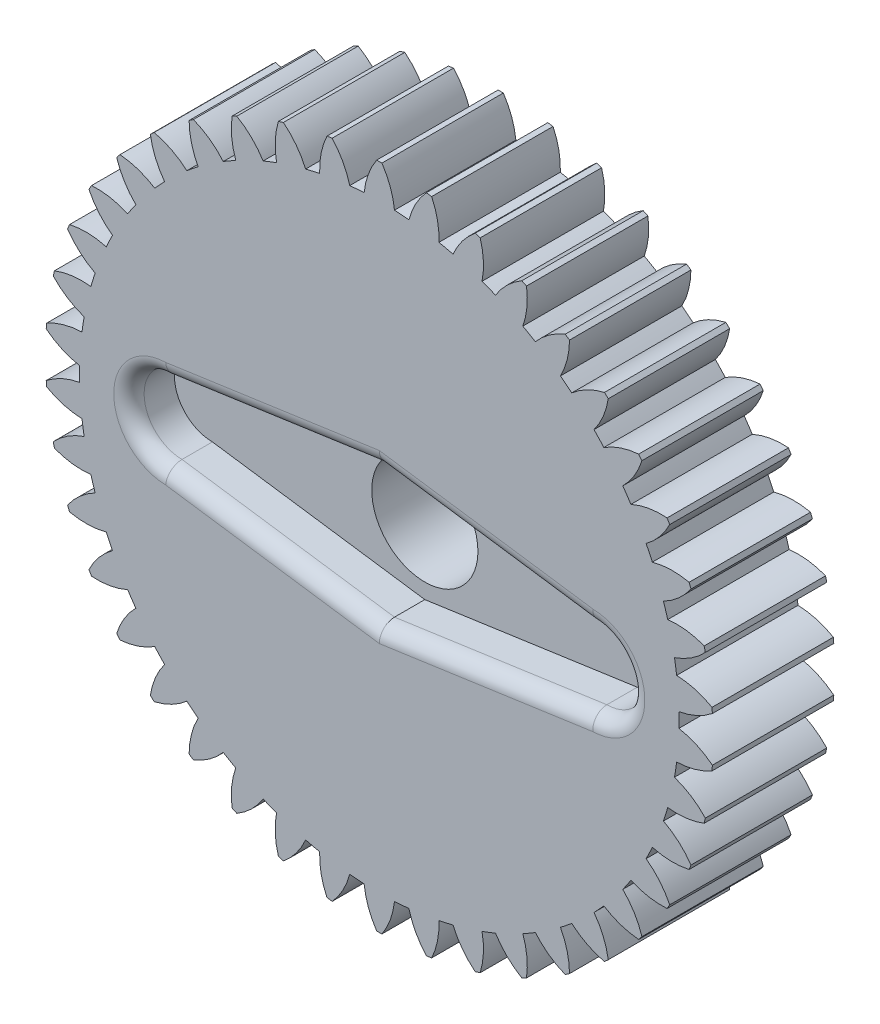
SolidWorks part; units mm, degrees
ref_plane "Front Plane" through (0, 0, 0) normal (0, 0, 1) x (1, 0, 0)
ref_plane "Top Plane" through (0, 0, 0) normal (0, 1, 0) x (1, 0, 0)
ref_plane "Right Plane" through (0, 0, 0) normal (1, 0, 0) x (0, 0, -1)
sketch "Sketch1" plane through (0, 0, 0) normal (0, 0, 1) x (1, 0, 0)
  line L0 (0, 0) -> (0, 23.4828) construction
  line L1 (0.1718, 22) -> (-0.1718, 22)
  line L2 (-1, 19.7247) -> (-0.1718, 22) construction
  line L3 (0.1718, 22) -> (1, 19.7247) construction
  line L4 (-1, 19.7247) -> (-1, 22.1675) construction
  circle A0 centre (0, 0) radius 19.75
  circle A1 centre (0, 0) radius 3.5
  circle A2 centre (0, 0) radius 22 construction
  arc A3 (-0.1718, 22) -> (-1, 19.7247) centre (3.9727, 19.2031) ccw
  arc A4 (0.1718, 22) -> (1, 19.7247) centre (-3.9727, 19.2031) cw
  point P13 (0, 22)
  dimension "D1" = 39.5
  dimension "D2" = 7
  dimension "D3" = 44
  dimension "D6" = 5
  dimension "D4" = 20
extrude "Boss-Extrude1" add sketch "Sketch1" along normal blind 8 contours A0 A1 region at (13.9097, 13.2223, 0)
extrude "Boss-Extrude2" add sketch "Sketch1<3>" along normal blind 8 contours A4 L1 A3 A0 region at (0, 20.6483, 0)
sketch "Sketch1<3>" plane through (0, 0, 0) normal (0, 0, 1) x (1, 0, 0) same geometry as "Sketch1"
pattern_circular "CirPattern1" count 42 over 360 about axis through (0, 0, 8) along (0, 0, 1) of "Boss-Extrude2"
sketch "Sketch2" plane through (0, 0, 8) normal (0, 0, 1) x (1, 0, 0)
  line L0 (-14, 0) -> (14, 0) construction
  line L1 (-16.5, 0) -> (-16.5, 6.0238) construction
  line L2 (0, -1.8271) -> (0, 2.3437) construction
  line L3 (-14, 2.5) -> (0, 4.5)
  line L4 (0, 4.5) -> (14, 2.5)
  line L5 (-14, -2.5) -> (0, -4.5)
  line L6 (0, -4.5) -> (14, -2.5)
  arc A0 (-1.26, -4.32) -> (1.26, -4.32) centre (0, 0) ccw
  arc A1 (-14, 2.5) -> (-14, -2.5) centre (-14, 0) ccw
  arc A2 (14, -2.5) -> (14, 2.5) centre (14, 0) ccw
  arc A3 (1.26, 4.32) -> (-1.26, 4.32) centre (0, 0) ccw
  dimension "D1" = 9
  dimension "D2" = 5
  dimension "D3" = 14
  dimension "D4" = 14
extrude "Cut-Extrude1" cut sketch "Sketch2" against normal blind 3 and the other way through all contours A2 L4 L3 A1 L5 L6
sketch "Sketch3" plane through (0, 0, 5) normal (0, 0, 1) x (1, 0, 0)
  line L0 (0, 2.6941) -> (0, -1.8899) construction
  line L1 (-14.45, 0) -> (14.45, 0) construction
  circle A0 centre (-14.45, 0) radius 1.33
  circle A1 centre (14.45, 0) radius 1.33
  dimension "D1" = 2.66
  dimension "D2" = 14.45
  dimension "D3" = 14.45
extrude "Cut-Extrude2" [suppressed] cut sketch "Sketch3" against normal through all
fillet "Fillet1" radius 1 6 edges at (-7, -3.5, 8) (7, -3.5, 8) (16.5, 0, 8) (7, 3.5, 8) (-16.5, 0, 8) (-7, 3.5, 8)
